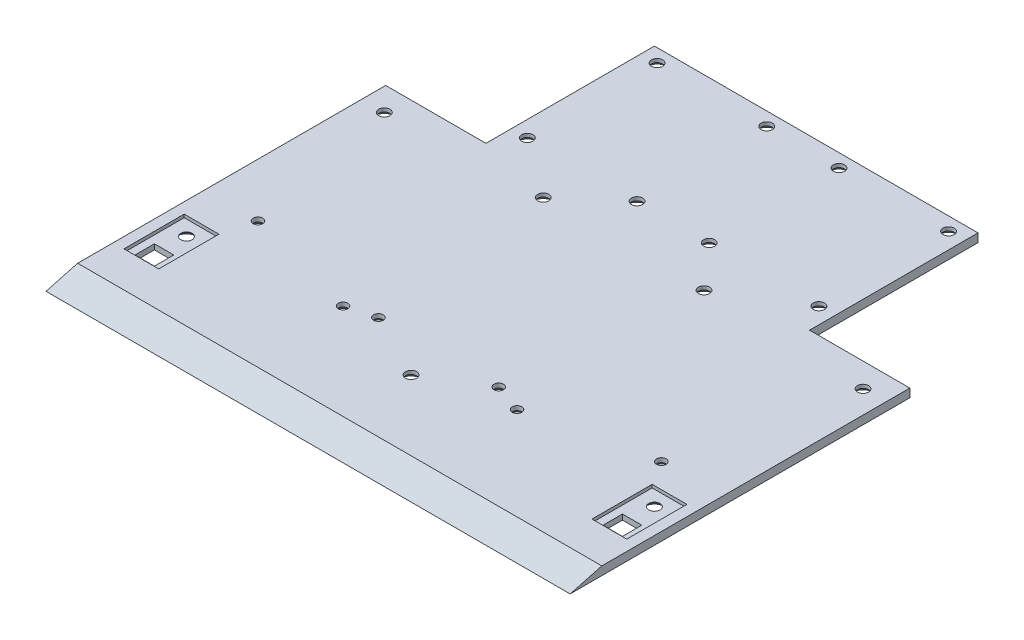
SolidWorks part; units mm, degrees
ref_plane "Alzado" through (0, 0, 0) normal (0, 0, 1) x (1, 0, 0)
ref_plane "Planta" through (0, 0, 0) normal (0, 1, 0) x (1, 0, 0)
ref_plane "Vista lateral" through (0, 0, 0) normal (1, 0, 0) x (0, 0, -1)
sketch "Croquis1" plane through (0, 0, 0) normal (1, 0, 0) x (0, 0, -1)
  line L0 (0, 0) -> (190, 0)
  line L1 (190, 0) -> (190, 3.17)
  line L2 (190, 3.17) -> (11.8306, 3.17)
  line L3 (0, 0) -> (11.8306, 3.17)
  dimension "D1" = 190
  dimension "D2" = 3.17
  dimension "D3" = 165
extrude "Saliente-Extruir1" add sketch "Croquis1" along normal blind 196
sketch "Croquis2" plane through (0, 0, 0) normal (0, -1, 0) x (-1, 0, 0)
  line L0 (0, 190) -> (0, 11.8306) construction
  line L1 (0, 127.0101) -> (-37.5, 127.0101)
  line L2 (0, 127.0101) -> (0, 190)
  line L3 (0, 190) -> (-37.5, 190)
  line L4 (-37.5, 127.0101) -> (-37.5, 190)
  line L5 (0, 127.0101) -> (-37.5, 190) construction
  line L6 (0, 190) -> (-37.5, 127.0101) construction
  line L7 (-196, 127.0101) -> (0, 127.0101) construction
  line L8 (-196, 190) -> (0, 190) construction
  line L9 (-37.5, 131.5) -> (-37.5, 190) construction
  point P4 (-18.75, 158.5051)
extrude "Cortar-Extruir1" cut sketch "Croquis2" against normal up to next
ref_plane "Plano1" through (98, 0, 0) normal (-1, 0, 0) x (0, 0, 1)
mirror "Simetría1" about plane through (98, 0, 0) normal (-1, 0, 0) of "Cortar-Extruir1"
sketch "Croquis3" plane through (0, 3.17, 0) normal (0, 1, 0) x (1, 0, 0)
  line L0 (196, 0) -> (0, 0) construction
  line L1 (4, 47.66) -> (17, 47.66)
  line L2 (4, 47.66) -> (4, 25.16)
  line L3 (4, 25.16) -> (17, 25.16)
  line L4 (17, 47.66) -> (17, 25.16)
  line L5 (4, 47.66) -> (17, 25.16) construction
  line L6 (4, 25.16) -> (17, 47.66) construction
  line L7 (0, 127.0101) -> (0, 11.8306) construction
  point P4 (10.5, 36.41)
  dimension "D1" = 25.16
  dimension "D2" = 22.5
  dimension "D3" = 13
  dimension "D4" = 4
extrude "Cortar-Extruir2" cut sketch "Croquis3" against normal blind 1.17
sketch "Croquis4" plane through (0, 2, 0) normal (0, 1, 0) x (1, 0, 0)
  line L0 (10.5, 25.16) -> (10.5, 26.41) construction
  line L1 (4, 25.16) -> (17, 25.16) construction
  line L2 (4, 26.41) -> (17, 26.41) construction
  line L3 (4, 47.66) -> (4, 25.16) construction
  line L4 (17, 25.16) -> (17, 47.66) construction
  line L5 (10.5, 26.41) -> (10.5, 33.66) construction
  line L6 (10.5, 30.035) -> (6.875, 30.035) construction
  line L7 (10.5, 30.035) -> (14.125, 30.035) construction
  line L8 (6.875, 30.035) -> (6.875, 26.41) construction
  line L9 (14.125, 30.035) -> (14.125, 33.66) construction
  dimension "D1" = 1.25
  dimension "D2" = 7.25
  dimension "D3" = 3.625
  dimension "D4" = 3.625
sketch "Croquis5" plane through (0, 2, 0) normal (0, 1, 0) x (1, 0, 0)
  line L1 (6.875, 26.41) -> (14.125, 26.41)
  line L2 (6.875, 26.41) -> (6.875, 33.66)
  line L3 (6.875, 33.66) -> (14.125, 33.66)
  line L4 (14.125, 26.41) -> (14.125, 33.66)
  line L5 (6.875, 26.41) -> (14.125, 33.66) construction
  line L6 (6.875, 33.66) -> (14.125, 26.41) construction
  point P4 (10.5, 30.035)
extrude "Cortar-Extruir3" cut sketch "Croquis5" against normal up to next
sketch "Croquis6" plane through (0, 2, 0) normal (0, 1, 0) x (1, 0, 0)
  line L0 (10.5, 47.66) -> (10.5, 46.41) construction
  line L1 (17, 47.66) -> (4, 47.66) construction
  line L2 (10.5, 46.41) -> (17, 46.41) construction
  line L3 (17, 25.16) -> (17, 47.66) construction
  line L4 (17, 46.41) -> (4, 46.41) construction
  line L5 (4, 47.66) -> (4, 25.16) construction
  circle A0 centre (10.5, 42.01) radius 1.6
  dimension "D2" = 3.2
  dimension "D1" = 1.25
  dimension "D3" = 4.4
extrude "Cortar-Extruir4" cut sketch "Croquis6" against normal up to next
mirror "Simetría2" about plane through (98, 0, 0) normal (-1, 0, 0) of "Cortar-Extruir2", "Cortar-Extruir4", "Cortar-Extruir3"
sketch "Sketch1" plane through (0, 3.17, 0) normal (0, 1, 0) x (1, 0, 0)
  circle A0 centre (8.5, 118.0101) radius 1.585
  circle A1 centre (187.5, 118.0101) radius 1.585
extrude "Cut-Extrude1" cut sketch "Sketch1" against normal up to next
sketch "Sketch2" plane through (0, 3.17, 0) normal (0, 1, 0) x (1, 0, 0)
  circle A0 centre (98.5, 38.0101) radius 1.585
extrude "Cut-Extrude2" cut sketch "Sketch2" against normal up to next
sketch "Sketch3" plane through (0, 3.17, 0) normal (0, 1, 0) x (1, 0, 0)
  circle A0 centre (43.5, 185) radius 1.5799
  circle A1 centre (84.5, 185) radius 1.585
  circle A2 centre (152.5, 185) radius 1.585
  circle A3 centre (111.5, 185) radius 1.585
  circle A4 centre (111.5, 136.5) radius 1.585
  circle A5 centre (152.5, 136.5) radius 1.585
  circle A6 centre (84.5, 136.5) radius 1.585
  circle A7 centre (43.5, 136.5) radius 1.585
extrude "Cut-Extrude3" cut sketch "Sketch3" against normal up to next
sketch "Sketch4" plane through (0, 3.17, 0) normal (0, 1, 0) x (1, 0, 0)
  circle A0 centre (65.7764, 120.1669) radius 1.6
  circle A1 centre (125.8764, 120.1669) radius 1.6
extrude "Cut-Extrude4" cut sketch "Sketch4" against normal blind 4.9
hole_wizard "Avellanado para tornillo con cabeza avellanada en cruz de M3.51" positions "3DSketch1" profile "Sketch5" countersink size "M3.5" standard "AS"
sketch3d "3DSketch1"
  line L0 (187.5, 0, -118.0101) -> (187.5, 3.17, -118.0101) construction
  line L1 (152.5, 0, -136.5) -> (152.5, 3.17, -136.5) construction
  line L2 (125.8764, 0, -120.1669) -> (125.8764, 3.17, -120.1669) construction
  line L3 (111.5, 0, -136.5) -> (111.5, 3.17, -136.5) construction
  line L4 (84.5, 0, -136.5) -> (84.5, 3.17, -136.5) construction
  line L5 (65.7764, 0, -120.1669) -> (65.7764, 3.17, -120.1669) construction
  line L6 (43.5, 0, -136.5) -> (43.5, 3.17, -136.5) construction
  line L7 (8.5, 0, -118.0101) -> (8.5, 3.17, -118.0101) construction
  line L8 (43.5, 0, -185) -> (43.5, 3.17, -185) construction
  line L9 (84.5, 0, -185) -> (84.5, 3.17, -185) construction
  line L10 (111.5, 0, -185) -> (111.5, 3.17, -185) construction
  line L11 (152.5, 0, -185) -> (152.5, 3.17, -185) construction
  line L12 (10.5, 0, -42.01) -> (10.5, 2, -42.01) construction
  line L13 (98.5, 0, -38.0101) -> (98.5, 3.17, -38.0101) construction
  line L14 (185.5, 0, -42.01) -> (185.5, 2, -42.01) construction
  point P0 (187.5, 0, -118.0101)
  point P4 (152.5, 0, -136.5)
  point P8 (125.8764, 0, -120.1669)
  point P12 (111.5, 0, -136.5)
  point P16 (84.5, 0, -136.5)
  point P20 (65.7764, 0, -120.1669)
  point P24 (43.5, 0, -136.5)
  point P28 (8.5, 0, -118.0101)
  point P32 (43.5, 0, -185)
  point P36 (84.5, 0, -185)
  point P40 (111.5, 0, -185)
  point P44 (152.5, 0, -185)
  point P48 (10.5, 0, -42.01)
  point P52 (98.5, 0, -38.0101)
  point P56 (185.5, 0, -42.01)
sketch "Sketch5" plane through (187.5, 0, -118.0101) normal (1, 0, 0) x (0, 0, -1)
  line L0 (0, 0) -> (0, 11.2618)
  line L1 (0, 11.2618) -> (2.1, 10)
  line L2 (2.1, 10) -> (2.1, 1.8348)
  line L3 (2.1, 1.8348) -> (4, 0)
  line L5 (4, 0) -> (0, 0)
  line L6 (-2.1, 1.8348) -> (-4, 0) construction
  line L10 (0, 11.2618) -> (-2.1, 10) construction
  line L11 (0, -6.35) -> (0, 107.95) construction
  dimension "Diámetro de taladro" = 4.2
  dimension "Profundidad de taladro" = 10
  dimension "Ángulo de avellanado cercano" = 8
  dimension "Ángulo de avellanado lejano" = 92
  dimension "Ángulo de perforador" = 118
sketch "Sketch6" plane through (0, 3.17, 0) normal (0, 1, 0) x (1, 0, 0)
  circle A0 centre (191.0671, 82.5578) radius 1.585
  circle A1 centre (97.6819, 83.0385) radius 1.585
  circle A2 centre (5.0671, 82.5578) radius 1.585
sketch "Sketch8" plane through (0, 0, 0) normal (0, 0.9659, 0.2588) x (1, 0, 0)
  circle A0 centre (28.1, 5.3001) radius 2.5
  circle A1 centre (79.9, 5.3001) radius 2.5
  circle A2 centre (116.1, 5.3001) radius 2.5
  circle A3 centre (167.9, 5.3001) radius 2.5
sketch "Sketch12" plane through (0, 3.17, 0) normal (0, 1, 0) x (1, 0, 0)
  circle A0 centre (20.0108, 59.2477) radius 1.5754
  circle A1 centre (63.4681, 47.6034) radius 1.5754
  circle A2 centre (73.7984, 50.4913) radius 1.5754
  circle A3 centre (118.7887, 50.4913) radius 1.5754
  circle A4 centre (129.5237, 46.6096) radius 1.5754
  circle A5 centre (173.3608, 56.7302) radius 1.5754
extrude "Cut-Extrude6" cut sketch "Sketch12" against normal blind 10
hole_wizard "Refrentado para tornillo tapón con cabeza plana de clavija de M31" positions "3DSketch5" profile "Sketch13" countersink size "M3" standard "Ansi Metric"
sketch3d "3DSketch5"
  line L0 (173.3608, 0, -56.7302) -> (173.3608, 3.17, -56.7302) construction
  line L1 (129.5237, 0, -46.6096) -> (129.5237, 3.17, -46.6096) construction
  line L2 (118.7887, 0, -50.4913) -> (118.7887, 3.17, -50.4913) construction
  line L3 (63.4681, 0, -47.6034) -> (63.4681, 3.17, -47.6034) construction
  line L4 (73.7984, 0, -50.4913) -> (73.7984, 3.17, -50.4913) construction
  line L5 (20.0108, 0, -59.2477) -> (20.0108, 3.17, -59.2477) construction
  point P0 (173.3608, 0, -56.7302)
  point P4 (129.5237, 0, -46.6096)
  point P8 (118.7887, 0, -50.4913)
  point P12 (63.4681, 0, -47.6034)
  point P16 (73.7984, 0, -50.4913)
  point P20 (20.0108, 0, -59.2477)
sketch "Sketch13" plane through (173.3608, 0, -56.7302) normal (1, 0, 0) x (0, 0, -1)
  line L0 (0, 0) -> (0, 11.0815)
  line L1 (0, 11.0815) -> (1.8, 10)
  line L2 (1.8, 10) -> (1.8, 1.56)
  line L3 (1.8, 1.56) -> (3.36, 0)
  line L5 (3.36, 0) -> (0, 0)
  line L6 (-1.8, 1.56) -> (-3.36, 0) construction
  line L10 (0, 11.0815) -> (-1.8, 10) construction
  line L11 (0, -6.35) -> (0, 107.95) construction
  dimension "Diámetro de taladro" = 3.6
  dimension "Profundidad de taladro" = 10
  dimension "Ángulo de avellanado cercano" = 6.72
  dimension "Ángulo de avellanado lejano" = 90
  dimension "Ángulo de perforador" = 118
